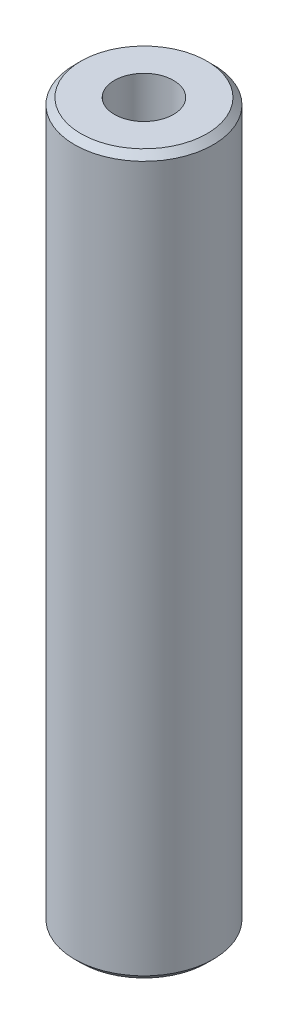
SolidWorks part; units mm, degrees
ref_plane "Front Plane" through (0, 0, 0) normal (0, 0, 1) x (1, 0, 0)
ref_plane "Top Plane" through (0, 0, 0) normal (0, 1, 0) x (1, 0, 0)
ref_plane "Right Plane" through (0, 0, 0) normal (1, 0, 0) x (0, 0, -1)
sketch "Sketch1" plane through (0, 0, 0) normal (0, 1, 0) x (1, 0, 0)
  circle A0 centre (0, 0) radius 10
  dimension "SHAFT_OD" = 20
extrude "Boss-Extrude1" add sketch "Sketch1" along normal blind 103.5768
sketch "Sketch2" plane through (0, 0, 0) normal (0, 1, 0) x (1, 0, 0)
  circle A0 centre (0, 0) radius 4.2629
  dimension "BORE_D" = 8.5258
extrude "Cut-Extrude1" cut sketch "Sketch2" along normal through all
chamfer "Chamfer1" distance 0.9175 angle 45 2 edges at (0, 103.5768, 10) (0, 0, 10)
